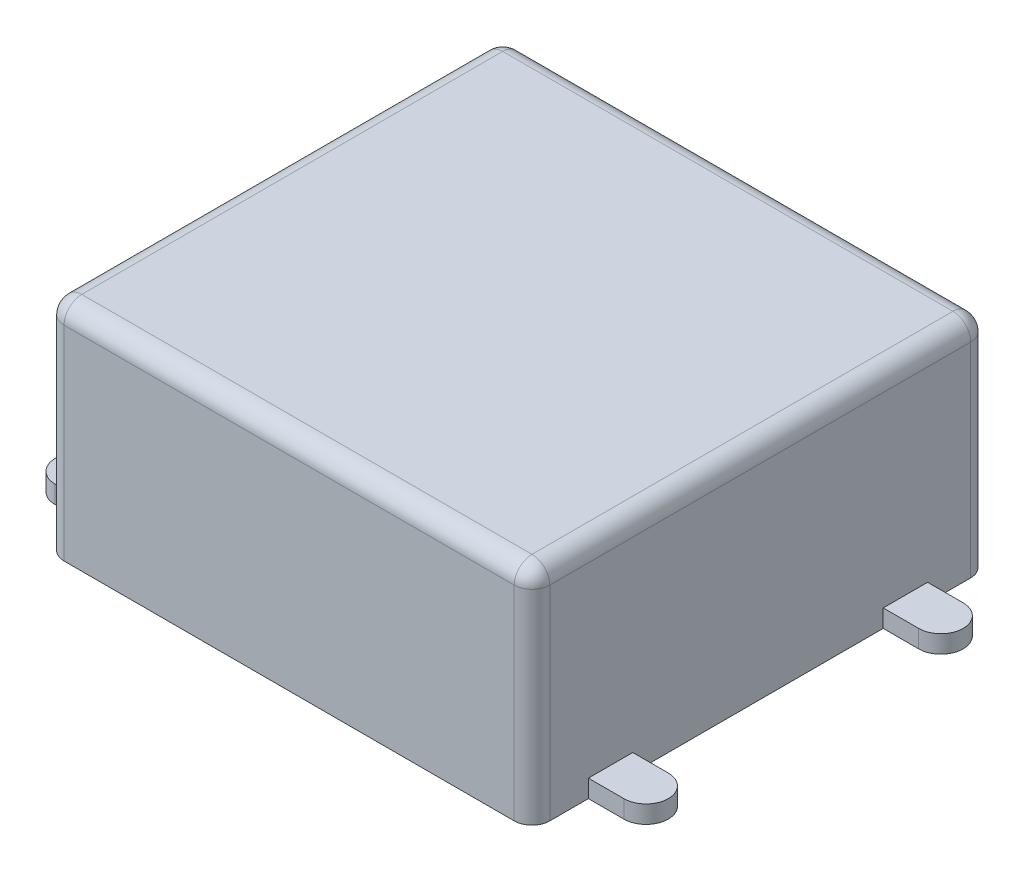
SolidWorks part; units mm, degrees
ref_plane "Front Plane" through (0, 0, 0) normal (0, 0, 1) x (1, 0, 0)
ref_plane "Top Plane" through (0, 0, 0) normal (0, 1, 0) x (1, 0, 0)
ref_plane "Right Plane" through (0, 0, 0) normal (1, 0, 0) x (0, 0, -1)
sketch "Sketch1" plane through (0, 0, 0) normal (0, 1, 0) x (1, 0, 0)
  line L0 (27.35, 25.7) -> (27.35, 20.7)
  line L1 (-24.15, 22.5) -> (24.15, 22.5)
  line L2 (-24.15, 22.5) -> (-24.15, -22.5)
  line L3 (-24.15, -22.5) -> (24.15, -22.5)
  line L4 (24.15, 22.5) -> (24.15, -22.5)
  line L5 (-24.15, 22.5) -> (24.15, -22.5) construction
  line L6 (-24.15, -22.5) -> (24.15, 22.5) construction
  line L7 (-27.35, 25.7) -> (27.35, 25.7)
  line L8 (-27.35, 25.7) -> (-27.35, -25.7)
  line L9 (-27.35, -25.7) -> (27.35, -25.7)
  line L10 (27.35, 25.7) -> (27.35, -25.7)
  line L11 (-27.35, 25.7) -> (27.35, -25.7) construction
  line L12 (-27.35, -25.7) -> (27.35, 25.7) construction
  line L14 (-27.35, -25.7) -> (-27.35, -20.7)
  line L15 (27.35, 18.8482) -> (31.35, 18.8482)
  line L16 (-27.35, 25.7) -> (-27.35, 20.7)
  line L17 (31.35, 13.8482) -> (27.35, 13.8482)
  line L18 (31.35, -14.3518) -> (27.35, -14.3518)
  line L19 (-27.35, -20.7) -> (-31.35, -20.7)
  line L20 (-31.35, -15.7) -> (-27.35, -15.7)
  line L21 (-31.35, 15.7) -> (-27.35, 15.7)
  line L22 (-27.35, 20.7) -> (-31.35, 20.7)
  line L23 (27.35, -19.3518) -> (31.35, -19.3518)
  arc A1 (31.35, 13.8482) -> (31.35, 18.8482) centre (31.35, 16.3482) ccw
  arc A2 (-31.35, -15.7) -> (-31.35, -20.7) centre (-31.35, -18.2) ccw
  arc A3 (-31.35, 15.7) -> (-31.35, 20.7) centre (-31.35, 18.2) cw
  arc A4 (31.35, -14.3518) -> (31.35, -19.3518) centre (31.35, -16.8518) cw
  point P0 (0, 0)
  point P6 (0, 0)
  point P26 (-29.35, -20.7)
  dimension "D1" = 45
  dimension "D2" = 48.3
  dimension "D3" = 54.7
  dimension "D4" = 51.4
  dimension "D5" = 5
  dimension "D6" = 5
extrude "Boss-Extrude1" add sketch "Sketch1" along normal blind 25 contours L10 L0 L7 L8 L9 L1 L4 L3 L2 | L4 L1 L2 L3 region at (26.5994, 0, -23.2) region at (0, 0, 0)
fillet "Fillet1" radius 2 8 edges at (-27.35, 12.5, -25.7) (27.35, 12.5, -25.7) (0, 25, -25.7) (-27.35, 25, 0) (-27.35, 12.5, 25.7) (0, 25, 25.7) (27.35, 25, 0) (27.35, 12.5, 25.7)
shell "Shell1" thickness 1.6 removed face at (0, 0, 0)
extrude "Boss-Extrude2" add sketch "Sketch1<3>" along normal blind 2 contours A4 L10 | L10 | L20 A2 L19 L8 | A3 L21 L8 L22 region at (30.3579, 0, -16.3482) region at (-30.3579, 0, -18.2) region at (30.3579, 0, 16.8518) region at (-30.3579, 0, 18.2)
sketch "Sketch1<3>" plane through (0, 0, 0) normal (0, 1, 0) x (1, 0, 0) same geometry as "Sketch1"
sketch "Sketch2" plane through (-25.75, 0, 0) normal (1, 0, 0) x (0, 0, -1)
  line L4 (9.5, 3.2) -> (0.5, 3.2)
  line L6 (0.5, 3.2) -> (9.5, 3.2)
  line L7 (0.5, 3.2) -> (0.5, 14.2)
  line L8 (0.5, 14.2) -> (9.5, 14.2)
  line L9 (9.5, 3.2) -> (9.5, 14.2)
  dimension "D1" = 11
extrude "Cut-Extrude1" cut sketch "Sketch2" against normal through all contours L4 L9 L8 L7 region at (-25.75, 8.7, -5)
